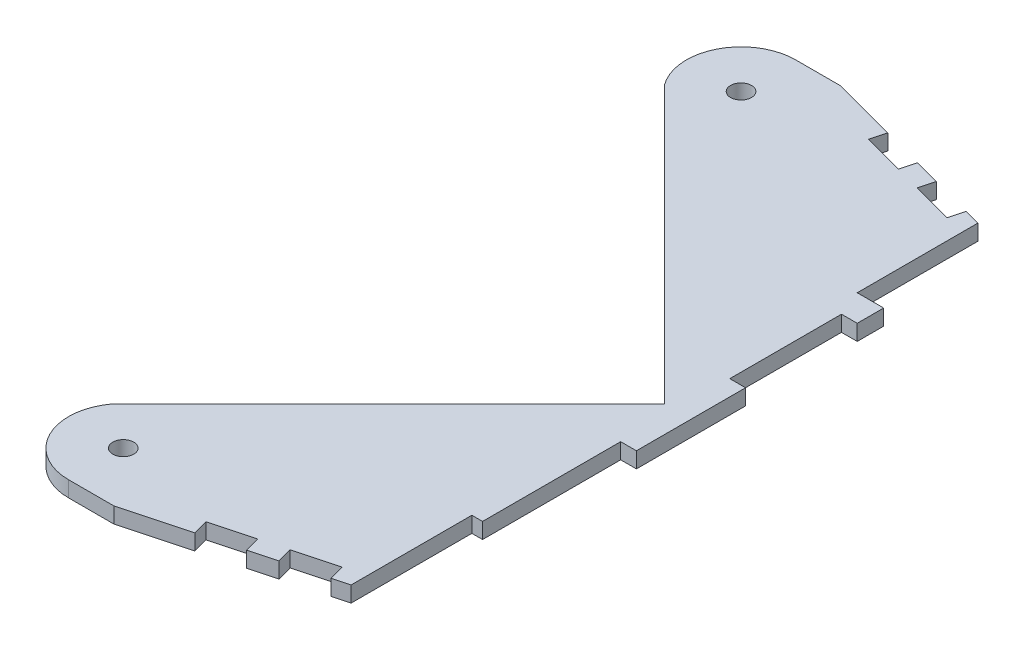
SolidWorks part; units mm, degrees
ref_plane "Front" through (0, 0, 0) normal (0, 0, 1) x (1, 0, 0)
ref_plane "Top" through (0, 0, 0) normal (0, 1, 0) x (1, 0, 0)
ref_plane "Right" through (0, 0, 0) normal (1, 0, 0) x (0, 0, -1)
ref_axis "side-side" through (80.9, 0, 0) along (-1, 0, 0)
ref_axis "up-down" through (0, 50, 0) along (0, -1, 0)
ref_axis "front-back" through (0, 0, -80.9) along (0, 0, 1)
sketch "Sketch1" plane through (0, 0, 0) normal (0, 1, 0) x (1, 0, 0)
  line L1 (0, 0) -> (-83.6295, 83.6295)
  line L3 (0, -94.8336) -> (-56.6019, -110)
  line L4 (-56.6019, 110) -> (0, 94.8336)
  line L5 (-70.3102, 110) -> (-56.6019, 110)
  line L6 (8, 58.293) -> (8, -58.293)
  line L7 (0, 0) -> (58.8362, 0) construction
  line L8 (-70.3102, -110) -> (-56.6019, -110)
  line L10 (0, 0) -> (-83.6295, -83.6295)
  line L12 (0, 94.8336) -> (0, 58.293)
  line L13 (0, 58.293) -> (8, 58.293)
  line L16 (0, -94.8336) -> (0, -58.293)
  line L17 (0, -58.293) -> (8, -58.293)
  circle A0 centre (-70.3102, 93.4511) radius 3.175
  circle A1 centre (-70.3102, -93.4511) radius 3.175
  arc A2 (-83.6295, 83.6295) -> (-70.3102, 110) centre (-70.3102, 93.4511) cw
  arc A3 (-83.6295, -83.6295) -> (-70.3102, -110) centre (-70.3102, -93.4511) ccw
  point P2 (0, 0)
  dimension "D5" = 6.35
  dimension "D1" = 64.6019
  dimension "D2" = 110
  dimension "D3" = 8
  dimension "D4" = 45
  dimension "D6" = 75
  dimension "D7" = 116.586
  dimension "D8" = 8
extrude "Boss-Extrude1" add sketch "Sketch1" along normal blind 4.7625
chamfer "Chamfer1" [suppressed] distance 10 distance2 10
sketch "Sketch3" plane through (0, 0, 0) normal (0, 1, 0) x (1, 0, 0)
  line L33 (-4.8296, 96.1276) -> (-17.1928, 99.4404)
  line L34 (-6.0623, 91.5274) -> (-4.8296, 96.1276)
  line L35 (-18.4255, 94.8401) -> (-6.0623, 91.5274)
  line L36 (-17.1928, 99.4404) -> (-18.4255, 94.8401)
  line L37 (-4.8296, 96.1276) -> (-17.1928, 99.4404)
  line L38 (-6.0623, 91.5274) -> (-4.8296, 96.1276)
  line L39 (-18.4255, 94.8401) -> (-6.0623, 91.5274)
  line L40 (-17.1928, 99.4404) -> (-18.4255, 94.8401)
  line L41 (-24.9202, 101.5109) -> (-37.2834, 104.8236)
  line L42 (-26.1529, 96.9107) -> (-24.9202, 101.5109)
  line L43 (-38.5161, 100.2234) -> (-26.1529, 96.9107)
  line L44 (-37.2834, 104.8236) -> (-38.5161, 100.2234)
  line L45 (-24.9202, 101.5109) -> (-37.2834, 104.8236)
  line L46 (-26.1529, 96.9107) -> (-24.9202, 101.5109)
  line L47 (-38.5161, 100.2234) -> (-26.1529, 96.9107)
  line L48 (-37.2834, 104.8236) -> (-38.5161, 100.2234)
  line L49 (8, 50.293) -> (3.2375, 50.293)
  line L50 (8, 16.51) -> (8, 50.293)
  line L51 (3.2375, 16.51) -> (8, 16.51)
  line L52 (3.2375, 50.293) -> (3.2375, 16.51)
  line L53 (8, 50.293) -> (3.2375, 50.293)
  line L54 (8, 16.51) -> (8, 50.293)
  line L55 (3.2375, 16.51) -> (8, 16.51)
  line L56 (3.2375, 50.293) -> (3.2375, 16.51)
  line L57 (-26.1529, -96.9107) -> (-38.5161, -100.2234)
  line L58 (-24.9202, -101.5109) -> (-26.1529, -96.9107)
  line L59 (-37.2834, -104.8236) -> (-24.9202, -101.5109)
  line L60 (-38.5161, -100.2234) -> (-37.2834, -104.8236)
  line L61 (-26.1529, -96.9107) -> (-38.5161, -100.2234)
  line L62 (-24.9202, -101.5109) -> (-26.1529, -96.9107)
  line L63 (-37.2834, -104.8236) -> (-24.9202, -101.5109)
  line L64 (-38.5161, -100.2234) -> (-37.2834, -104.8236)
  line L65 (-6.0623, -91.5274) -> (-18.4255, -94.8401)
  line L66 (-4.8296, -96.1276) -> (-6.0623, -91.5274)
  line L67 (-17.1928, -99.4404) -> (-4.8296, -96.1276)
  line L68 (-18.4255, -94.8401) -> (-17.1928, -99.4404)
  line L69 (-6.0623, -91.5274) -> (-18.4255, -94.8401)
  line L70 (-4.8296, -96.1276) -> (-6.0623, -91.5274)
  line L71 (-17.1928, -99.4404) -> (-4.8296, -96.1276)
  line L72 (-18.4255, -94.8401) -> (-17.1928, -99.4404)
  line L73 (3.2375, -16.51) -> (3.2375, -50.293)
  line L74 (8, -16.51) -> (3.2375, -16.51)
  line L75 (8, -50.293) -> (8, -16.51)
  line L76 (3.2375, -50.293) -> (8, -50.293)
  line L77 (3.2375, -16.51) -> (3.2375, -62.7995)
  line L78 (8, -16.51) -> (3.2375, -16.51)
  line L79 (8, -62.7995) -> (8, -16.51)
  line L80 (3.2375, -62.7995) -> (8, -62.7995)
  point P29 (-1.8847, -38.857)
  dimension "D1" = 0
  dimension "D2" = 0
  dimension "D3" = 0
  dimension "D4" = 0
  dimension "D5" = 0
  dimension "D6" = 0
extrude "Cut-Extrude2" cut sketch "Sketch3" along normal blind 10
